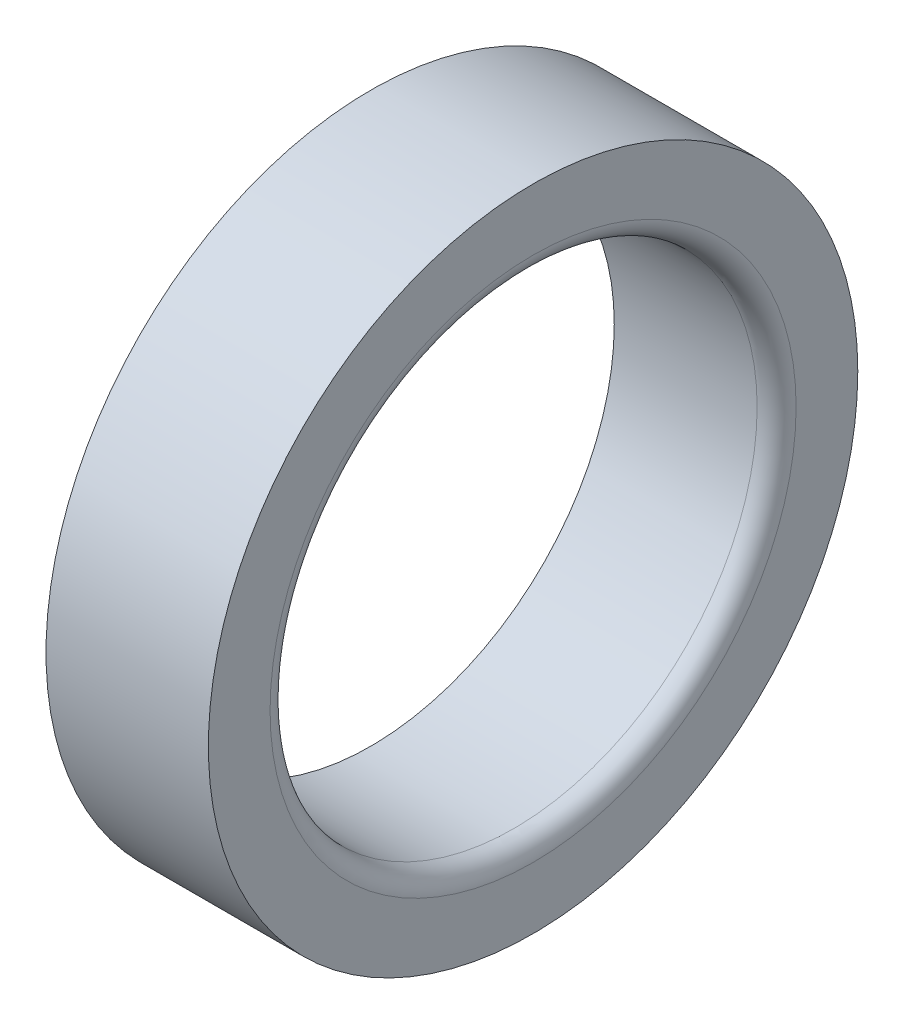
SolidWorks part; units mm, degrees
material "316L ST. STL."
ref_plane "Front" through (0, 0, 0) normal (0, 0, 1) x (1, 0, 0)
ref_plane "Top" through (0, 0, 0) normal (0, 1, 0) x (1, 0, 0)
ref_plane "Right" through (0, 0, 0) normal (1, 0, 0) x (0, 0, -1)
ref_axis "Axis1" through (0, 50, 0) along (0, -1, 0)
sketch "Sketch1" plane through (0, 0, 0) normal (1, 0, 0) x (0, 0, -1)
  circle A0 centre (0, 0) radius 12.7
  dimension "D1" = 25.4
extrude "Boss-Extrude1" add sketch "Sketch1" along normal blind 6.35
sketch "Sketch2" plane through (6.35, 0, 0) normal (1, 0, 0) x (0, 0, -1)
  circle A0 centre (0, 0) radius 9.525
  dimension "D1" = 19.05
extrude "Cut-Extrude1" cut sketch "Sketch2" against normal up to next
fillet "Fillet1" radius 0.762 1 edges at (6.35, 0, -9.525)
